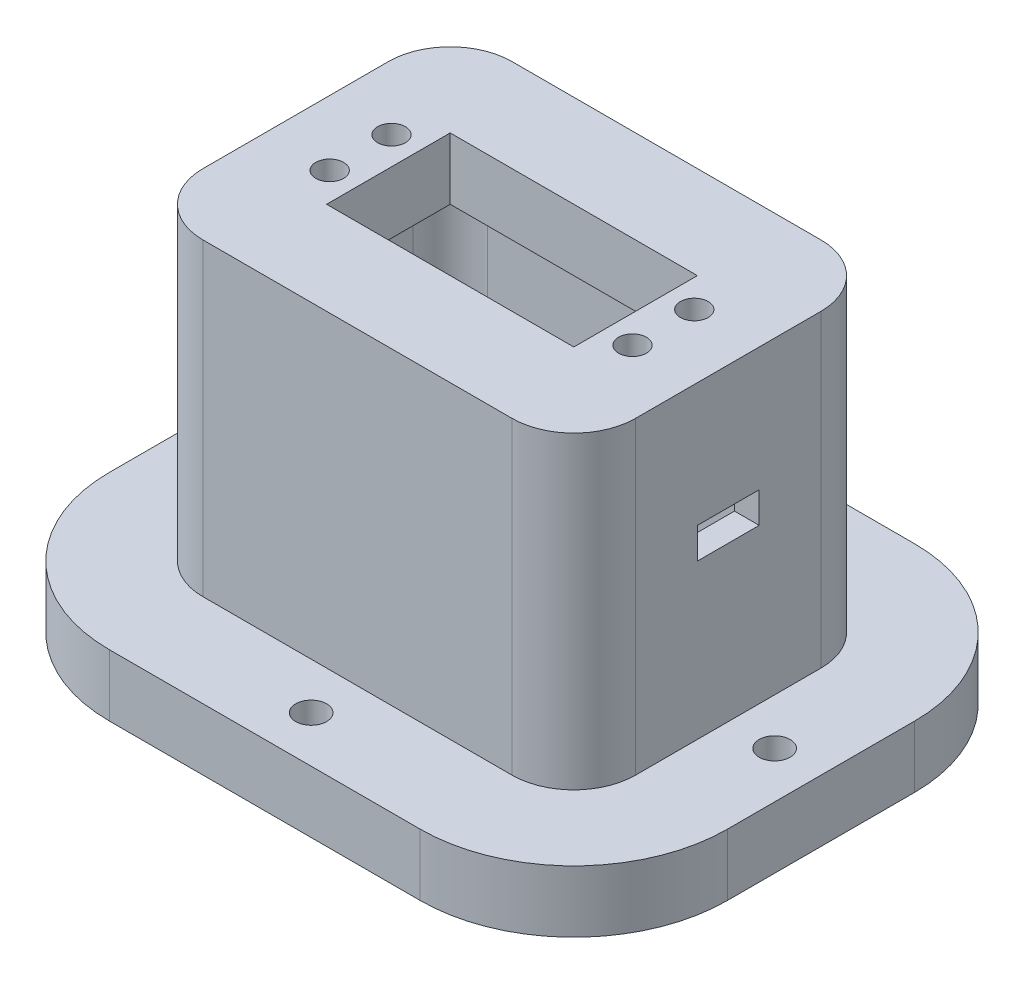
SolidWorks part; units mm, degrees
ref_plane "Alzado" through (0, 0, 0) normal (0, 0, 1) x (1, 0, 0)
ref_plane "Planta" through (0, 0, 0) normal (0, 1, 0) x (1, 0, 0)
ref_plane "Vista lateral" through (0, 0, 0) normal (1, 0, 0) x (0, 0, -1)
sketch "Croquis1" plane through (0, 0, 0) normal (0, 1, 0) x (1, 0, 0)
  line L1 (35, -25) -> (-35, -25)
  line L2 (35, -25) -> (35, 25)
  line L3 (35, 25) -> (-35, 25)
  line L4 (-35, -25) -> (-35, 25)
  line L5 (35, -25) -> (-35, 25) construction
  line L6 (35, 25) -> (-35, -25) construction
  line L8 (-20, -10) -> (20, -10)
  line L9 (-20, -10) -> (-20, 10)
  line L10 (-20, 10) -> (20, 10)
  line L11 (20, -10) -> (20, 10)
  point P0 (0, 0)
  point P12 (20, 0)
  dimension "D1" = 70
  dimension "D2" = 50
  dimension "D3" = 15
  dimension "D4" = 40
  dimension "D5" = 20
  dimension "D6" = 15
extrude "Saliente-Extruir1" add sketch "Croquis1" along normal blind 10
sketch "Croquis2" plane through (0, 10, 0) normal (0, 1, 0) x (1, 0, 0)
  line L0 (20, -10) -> (20, 10) construction
  line L3 (-20, -10) -> (20, -10) construction
  line L4 (20, 0) -> (72.7854, 0) construction
  line L5 (0, 10) -> (0, -10) construction
  line L6 (20, 10) -> (-20, 10) construction
  circle A0 centre (24.5, -5) radius 2.25
  circle A1 centre (24.5, 5) radius 2.25
  circle A2 centre (-24.5, -5) radius 2.25
  circle A3 centre (-24.5, 5) radius 2.25
  dimension "D3" = 4.5
  dimension "D1" = 4.5
  dimension "D2" = 5
extrude "Cortar-Extruir1" cut sketch "Croquis2" against normal blind 10
fillet "Redondeo3" radius 10 4 edges at (35, 5, 25) (-35, 5, 25) (-35, 5, -25) (35, 5, -25)
sketch "Croquis3" plane through (0, 0, 0) normal (0, -1, 0) x (1, 0, 0)
  line L0 (-25, 21) -> (25, 21)
  line L1 (-25, 25) -> (25, 25)
  line L2 (-35, 15) -> (-35, -15)
  line L3 (-25, -25) -> (25, -25)
  line L4 (35, 15) -> (35, -15)
  line L5 (31, 15) -> (31, -15)
  line L6 (-25, -21) -> (25, -21)
  line L7 (-31, 15) -> (-31, -15)
  arc A0 (35, 15) -> (25, 25) centre (25, 15) ccw
  arc A1 (35, -15) -> (25, -25) centre (25, -15) cw
  arc A2 (-25, -25) -> (-35, -15) centre (-25, -15) cw
  arc A3 (-35, 15) -> (-25, 25) centre (-25, 15) cw
  arc A4 (31, 15) -> (25, 21) centre (25, 15) ccw
  arc A5 (31, -15) -> (25, -21) centre (25, -15) cw
  arc A6 (-25, -21) -> (-31, -15) centre (-25, -15) cw
  arc A7 (-31, 15) -> (-25, 21) centre (-25, 15) cw
  point P6 (35, 25)
  point P9 (35, -25)
  point P14 (-35, 25)
  dimension "D3" = 10
  dimension "D1" = 70
  dimension "D2" = 50
  dimension "D4" = 4
extrude "Saliente-Extruir2" add sketch "Croquis3" along normal blind 40
sketch "Croquis4" plane through (0, -40, 0) normal (0, -1, 0) x (1, 0, 0)
  line L0 (-25.1526, 40) -> (25.1526, 40)
  line L5 (50, 15.1526) -> (50, -15.1526)
  line L6 (-25.1526, -40) -> (25.1526, -40)
  line L7 (-50, 15.1526) -> (-50, -15.1526)
  line L9 (-25, 21) -> (25, 21)
  line L10 (-31, 15) -> (-31, -15)
  line L11 (-25, -21) -> (25, -21)
  line L12 (31, 15) -> (31, -15)
  arc A4 (25.1526, 40) -> (50, 15.1526) centre (25.1526, 15.1526) cw
  arc A5 (50, -15.1526) -> (25.1526, -40) centre (25.1526, -15.1526) cw
  arc A6 (-25.1526, -40) -> (-50, -15.1526) centre (-25.1526, -15.1526) cw
  arc A7 (-50, 15.1526) -> (-25.1526, 40) centre (-25.1526, 15.1526) cw
  arc A9 (-25, -21) -> (-31, -15) centre (-25, -15) cw
  arc A10 (25, -21) -> (31, -15) centre (25, -15) ccw
  arc A11 (31, 15) -> (25, 21) centre (25, 15) ccw
  arc A12 (-31, 15) -> (-25, 21) centre (-25, 15) cw
  point P6 (35, 25)
  point P9 (35, -25)
  point P10 (31, -21)
  point P13 (31, 21)
  point P14 (-35, 25)
  point P30 (-31, 21)
  dimension "D3" = 6
  dimension "D1" = 62
  dimension "D2" = 42
extrude "Saliente-Extruir3" add sketch "Croquis4" along normal blind 10 separate body
sketch "Croquis5" plane through (0, -40, 0) normal (0, 1, 0) x (1, 0, 0)
  line L0 (-35, 15) -> (-35, -15) construction
  line L3 (-25, 25) -> (25, 25) construction
  line L6 (-11.9487, 0) -> (11.9487, 0) construction
  line L7 (0, 10.9885) -> (0, -12.6955) construction
  circle A0 centre (-42.5, 0) radius 2.5
  circle A1 centre (0, 32.5) radius 2.5
  circle A2 centre (0, -32.5) radius 2.5
  circle A3 centre (42.5, 0) radius 2.5
  dimension "D1" = 7.5
  dimension "D2" = 7.5
  dimension "D3" = 5
  dimension "D4" = 5
extrude "Cortar-Extruir2" cut sketch "Croquis5" against normal blind 10
sketch "Croquis6" plane through (35, 0, 0) normal (1, 0, 0) x (0, 0, -1)
  line L1 (-5, -10) -> (5, -10)
  line L2 (-5, -10) -> (-5, -15)
  line L3 (-5, -15) -> (5, -15)
  line L4 (5, -10) -> (5, -15)
  point P3 (5, -10)
extrude "Cortar-Extruir3" cut sketch "Croquis6" against normal blind 15
